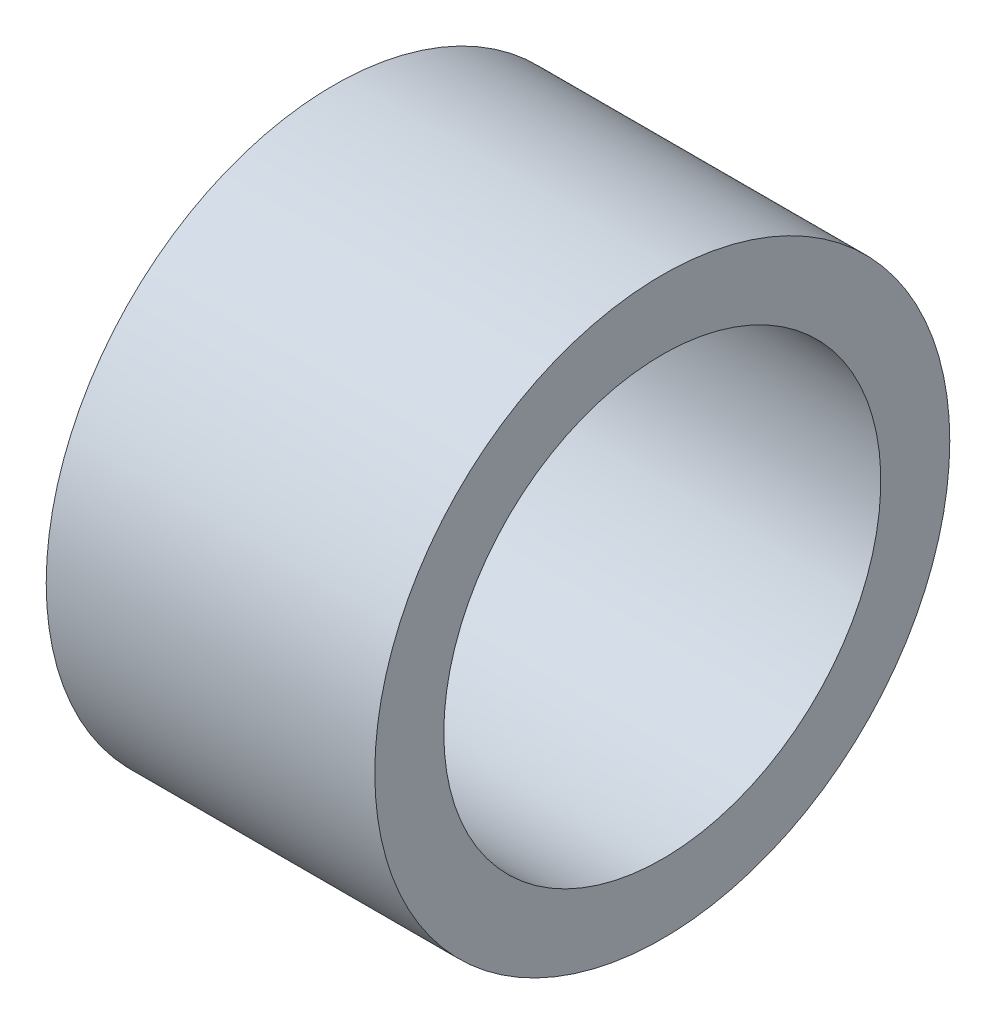
SolidWorks part; units mm, degrees
material "Nylon 6/10"
ref_plane "Front Plane" through (0, 0, 0) normal (0, 0, 1) x (1, 0, 0)
ref_plane "Top Plane" through (0, 0, 0) normal (0, 1, 0) x (1, 0, 0)
ref_plane "Right Plane" through (0, 0, 0) normal (1, 0, 0) x (0, 0, -1)
sketch "Sketch1" plane through (0, 0, 0) normal (0, 0, 1) x (1, 0, 0)
  line L0 (38.1, -11.935) -> (38.1, 10.1355) construction
  line L1 (38.1, 5.5563) -> (44.45, 5.5563)
  line L2 (38.1, 5.5563) -> (38.1, 4.2228)
  line L3 (38.1, 4.2228) -> (44.45, 4.2228)
  line L4 (44.45, 5.5563) -> (44.45, 4.2228)
  line L5 (0, 0) -> (42.6651, 0) construction
  line L7 (56.8854, 3.9688) -> (-54.7878, 3.9688) construction
  dimension "D1" = 0.254
  dimension "D2" = 11.1125
  dimension "D3" = 6.35
revolve "Revolve1" add sketch "Sketch1" angle 360 about L5
